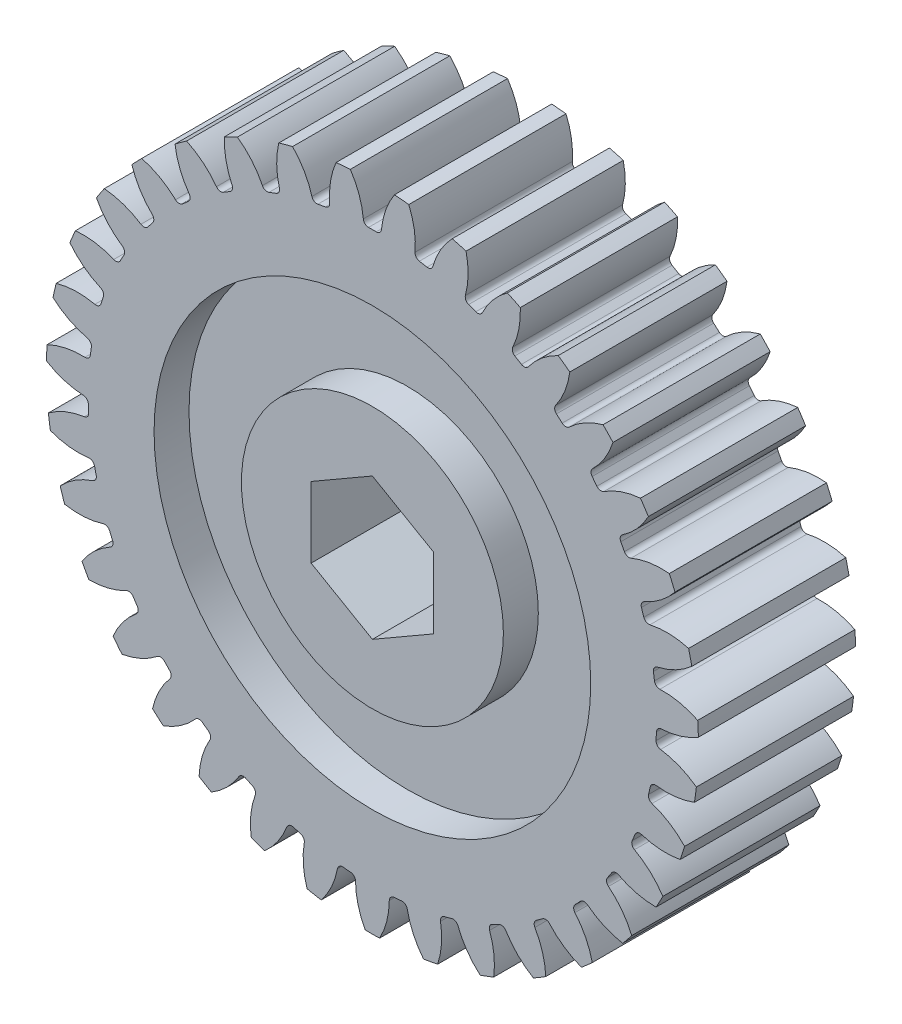
SolidWorks part; units mm, degrees
ref_plane "Ebene vorne" through (0, 0, 0) normal (0, 0, 1) x (1, 0, 0)
ref_plane "Ebene oben" through (0, 0, 0) normal (0, 1, 0) x (1, 0, 0)
ref_plane "Ebene rechts" through (0, 0, 0) normal (1, 0, 0) x (0, 0, -1)
sketch "Skizze1" plane through (0, 0, 0) normal (0, 0, 1) x (1, 0, 0)
  circle A0 centre (0, 0) radius 18.6665
  dimension "D1" = 37.333
extrude "Aufsatz-Linear austragen1" add sketch "Skizze1" along normal mid plane 9
sketch "Skizze4" plane through (0, 0, 4.5) normal (0, 0, 1) x (1, 0, 0)
  circle A0 centre (0, 0) radius 7.5
  circle A1 centre (0, 0) radius 12.5
  dimension "D1" = 25
  dimension "D2" = 15
extrude "Schnitt-Linear austragen2" cut sketch "Skizze4" against normal blind 2
sketch "Skizze6" plane through (0, 0, 4.5) normal (0, 0, 1) x (1, 0, 0)
  line L0 (0, 0) -> (0, 18.6665) construction
  line L1 (-0.2199, 16.267) -> (0.2199, 16.267)
  circle A0 centre (0, 0) radius 18.6665 construction
  arc A1 (0.5184, 16.5377) -> (2.08, 19.547) centre (5.0567, 16.0926) cw
  arc A2 (-0.5184, 16.5377) -> (-2.08, 19.547) centre (-5.0567, 16.0926) ccw
  arc A3 (-2.08, 19.547) -> (2.08, 19.547) centre (0, 1.6676) cw
  arc A4 (0.2199, 16.267) -> (0.5184, 16.5377) centre (0.2199, 16.567) ccw
  arc A5 (-0.5184, 16.5377) -> (-0.2199, 16.267) centre (-0.2199, 16.567) ccw
  point P13 (0, 16.267)
  point P16 (0.5, 16.267)
  point P19 (-0.5, 16.267)
  dimension "D5" = 4.56
  dimension "D6" = 18
  dimension "D7" = 0.3
  dimension "D1" = 0.5
  dimension "D2" = 16.267
  dimension "D3" = 1.58
  dimension "D4" = 3.28
extrude "Schnitt-Linear austragen3" cut sketch "Skizze6" against normal through all
pattern_circular "Kreismuster1" count 35 over 360 about axis through (0, 0, 2.5) along (0, 0, 1) of "Schnitt-Linear austragen3" reverse direction yes
sketch "Skizze8" plane through (0, 0, -4.5) normal (0, 0, -1) x (-1, 0, 0)
  circle A0 centre (0, 0) radius 6
extrude "Aufsatz-Linear austragen2" add sketch "Skizze8" along normal blind 1 contours A0
sketch "Skizze7" plane through (0, 0, 4.5) normal (0, 0, 1) x (1, 0, 0)
  line L1 (0, 4.05) -> (-3.5074, 2.025)
  line L2 (-3.5074, 2.025) -> (-3.5074, -2.025)
  line L3 (-3.5074, -2.025) -> (0, -4.05)
  line L4 (0, -4.05) -> (3.5074, -2.025)
  line L5 (3.5074, -2.025) -> (3.5074, 2.025)
  line L6 (3.5074, 2.025) -> (0, 4.05)
  circle A0 centre (0, 0) radius 3.5074 construction
  dimension "D1" = 8.1
extrude "Schnitt-Linear austragen4" cut sketch "Skizze7" against normal through all
